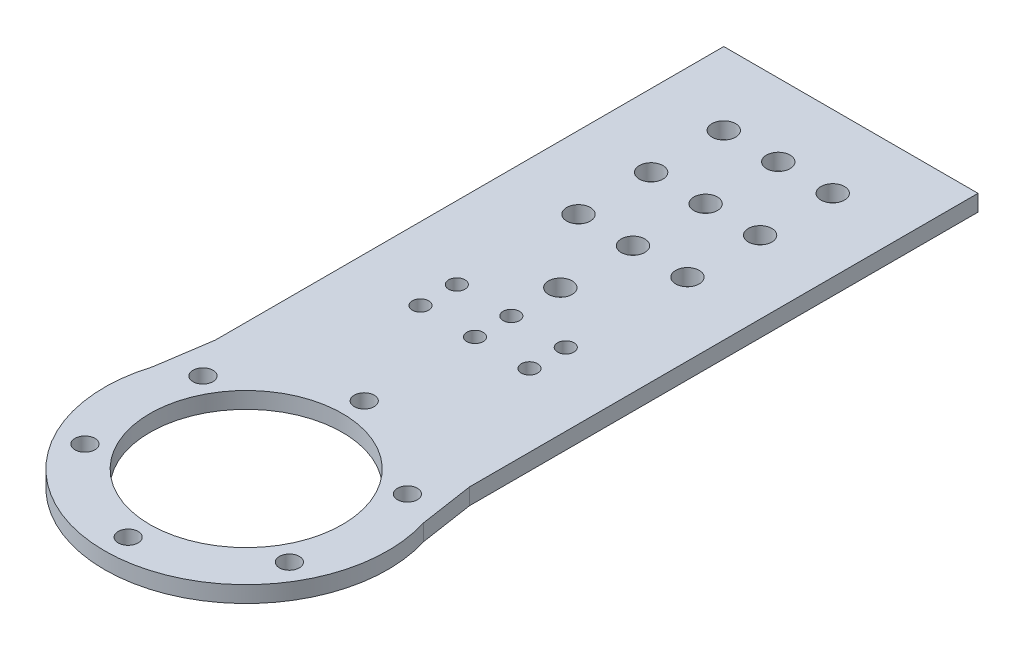
SolidWorks part; units mm, degrees
ref_plane "Front Plane" through (0, 0, 0) normal (0, 0, 1) x (1, 0, 0)
ref_plane "Top Plane" through (0, 0, 0) normal (0, 1, 0) x (1, 0, 0)
ref_plane "Right Plane" through (0, 0, 0) normal (1, 0, 0) x (0, 0, -1)
sketch "Sketch1" plane through (0, 0, 0) normal (0, 1, 0) x (1, 0, 0)
  circle A0 centre (0, 0) radius 45 construction
  circle A1 centre (0, 0) radius 39
  circle A2 centre (0, 0) radius 26.5
  circle A3 centre (0, 0) radius 32.5 construction
  dimension "D1" = 90
  dimension "D2" = 65
  dimension "D3" = 78
  dimension "D4" = 53
extrude "Boss-Extrude1" add sketch "Sketch1" along normal mid plane 4.5
sketch "Sketch3" plane through (0, 0, 0) normal (0, 1, 0) x (1, 0, 0)
  line L0 (0, 0) -> (0, 78) construction
  line L2 (-25, 78) -> (25, 78)
  line L3 (-25, 78) -> (-25, 26.5)
  line L4 (-25, 26.5) -> (25, 26.5)
  line L5 (25, 78) -> (25, 26.5)
  line L6 (0, 26.5) -> (0, 78) construction
  line L7 (-25, 52.25) -> (25, 52.25) construction
  circle A0 centre (0, 0) radius 26.5 construction
  point P3 (0, 52.25)
  dimension "D1" = 78
  dimension "D2" = 50
extrude "Boss-Extrude2" add sketch "Sketch3" along normal mid plane 4.5
sketch "Sketch4" plane through (0, 0, 0) normal (0, 1, 0) x (1, 0, 0)
  line L0 (-25, 53.9666) -> (-37.4668, 10.8276)
  line L1 (-25, 78) -> (-25, 29.9333) construction
  line L2 (-37.4668, 10.8276) -> (-25, 29.9333)
  line L3 (-25, 29.9333) -> (-25, 53.9666)
  line L4 (0, 0) -> (0, 78) construction
  line L5 (25, 78) -> (-25, 78) construction
  line L6 (37.4668, 10.8276) -> (25, 29.9333)
  line L7 (25, 53.9666) -> (37.4668, 10.8276)
  line L8 (25, 29.9333) -> (25, 53.9666)
  circle A0 centre (0, 0) radius 39 construction
extrude "Boss-Extrude3" [suppressed] add sketch "Sketch4" along normal mid plane 4.5
sketch "Sketch6" plane through (0, 0, 0) normal (0, 1, 0) x (1, 0, 0)
  line L0 (0, 0) -> (0, 96.5) construction
  line L1 (-35, 166.5) -> (-35, 26.5)
  line L2 (-35, 166.5) -> (35, 166.5)
  line L4 (35, 166.5) -> (35, 26.5)
  line L5 (0, 26.5) -> (0, 166.5) construction
  line L6 (-35, 96.5) -> (35, 96.5) construction
  line L7 (-35, 26.5) -> (-39, 0)
  line L8 (35, 26.5) -> (39, 0)
  line L9 (39, 0) -> (16.5208, 26.5)
  line L10 (16.5208, 26.5) -> (-14.9815, 26.5)
  line L11 (-14.9815, 26.5) -> (-39, 0)
  circle A0 centre (0, 0) radius 26.5 construction
  circle A1 centre (0, 0) radius 39 construction
  dimension "D1" = 70
  dimension "D2" = 140
extrude "Boss-Extrude4" add sketch "Sketch6" along normal mid plane 4.5
sketch "Sketch2" plane through (0, 0, 0) normal (0, 1, 0) x (1, 0, 0)
  circle A0 centre (0, 0) radius 32.5 construction
  circle A1 centre (0, 32.5) radius 2.75
  dimension "D1" = 65
  dimension "D2" = 5.5
extrude "Cut-Extrude1" cut sketch "Sketch2" against normal through all both and the other way through all contours A1
pattern_circular "CirPattern1" count 6 over 360 about axis through (0, 2.25, 0) along (0, 1, 0) of "Cut-Extrude1"
sketch "Sketch5" plane through (0, 2.25, 0) normal (0, 1, 0) x (1, 0, 0)
  line L0 (-25, 73) -> (25, 73) construction
  line L4 (35, 166.5) -> (-35, 166.5) construction
  circle A0 centre (0, 73) radius 2.25
  dimension "D1" = 4.5
  dimension "D3" = 93.5
extrude "Cut-Extrude2" cut sketch "Sketch5" against normal through all both and the other way through all
pattern_linear "LPattern1" count 2 spacing 15 along (1, 0, 0) count 2 spacing 10 along (0, 0, 1) of "Cut-Extrude2"
pattern_linear "LPattern2" count 2 spacing 15 along (-1, 0, 0) count 2 spacing 10 along (0, 0, 1) of "Cut-Extrude2"
sketch "Sketch7" plane through (0, 2.25, 0) normal (0, 1, 0) x (1, 0, 0)
  line L0 (0, 0) -> (0, 166.5) construction
  line L1 (35, 166.5) -> (-35, 166.5) construction
  line L2 (-15, 146.5) -> (15, 146.5) construction
  circle A0 centre (-15, 146.5) radius 3.25
  circle A1 centre (15, 146.5) radius 3.25
  point P8 (0, 146.5)
  dimension "D1" = 6.5
  dimension "D2" = 20
  dimension "D3" = 30
extrude "Cut-Extrude3" cut sketch "Sketch7" against normal through all both and the other way through all
pattern_linear "LPattern3" count 3 spacing 20 along (0, 0, 1) of "Cut-Extrude3"
sketch "Sketch8" plane through (0, 2.25, 0) normal (0, 1, 0) x (1, 0, 0)
  line L0 (0, 0) -> (0, 166.5) construction
  line L1 (35, 166.5) -> (-35, 166.5) construction
  circle A0 centre (0, 146.5) radius 3.25
  dimension "D1" = 6.5
  dimension "D2" = 20
extrude "Cut-Extrude4" cut sketch "Sketch8" against normal blind 10
pattern_linear "LPattern4" count 4 spacing 20 along (0, 0, 1) of "Cut-Extrude4"
